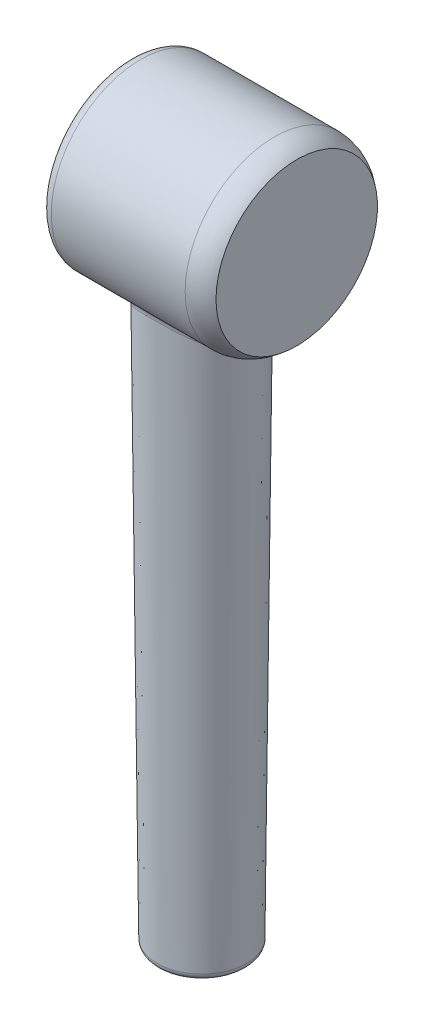
SolidWorks part; units mm, degrees
ref_plane "Front Plane" through (0, 0, 0) normal (0, 0, 1) x (1, 0, 0)
ref_plane "Top Plane" through (0, 0, 0) normal (0, 1, 0) x (1, 0, 0)
ref_plane "Right Plane" through (0, 0, 0) normal (1, 0, 0) x (0, 0, -1)
sketch "Sketch1" plane through (0, 0, 0) normal (0, 0, 1) x (1, 0, 0)
  line L0 (0, 128.3388) -> (0, 0) construction
  line L1 (0, 0) -> (119.2182, 0) construction
  line L6 (-55.114, 40) -> (84.2997, 40) construction
  line L7 (-32.5, 40) -> (-32.5, 0)
  line L8 (-32.5, 0) -> (42.5, 0)
  line L9 (42.5, 0) -> (42.5, 40)
  line L10 (42.5, 40) -> (-32.5, 40)
  line L11 (20, -250) -> (-20, -250)
  line L12 (-20, -250) -> (-22.9, 40)
  line L14 (0, -250) -> (0, 40)
  line L15 (20, -250) -> (22.9, 40) construction
  arc A0 (32.5, 0) -> (42.5, 3.8197) centre (32.5, 15) ccw
  point P2 (29.7647, 15.3345)
  point P4 (-22.5, 0)
  point P22 (22.5, 0)
  point P23 (30.298, 15.818)
  dimension "D7" = 10
  dimension "D8" = 15
  dimension "D1" = 40
  dimension "D2" = 10
  dimension "D3" = 22.5
  dimension "D4" = 20
  dimension "D5" = 250
  dimension "D6" = 20
revolve "Revolve1" add sketch "Sketch1" angle 360 about L6 region at (-27.5993, 19.8639, 0) region at (-11.3503, 20.0587, 0) region at (21.1162, 20.1343, 0)
revolve "Revolve2" add sketch "Sketch1<3>" angle 360 about L0 region at (-11.3503, 20.0587, 0) region at (-10.6373, -122.549, 0)
sketch "Sketch1<3>" plane through (0, 0, 0) normal (0, 0, 1) x (1, 0, 0) same geometry as "Sketch1"
combine bodies "Combine1" operation type add bodies to combine 101 102
fillet "Fillet1" radius 5 2 edges at (14.8869, 3.7553, 16.921) (-32.5, 40, 40)
fillet "Fillet2" radius 3 1 edges at (0, -250, 20)
